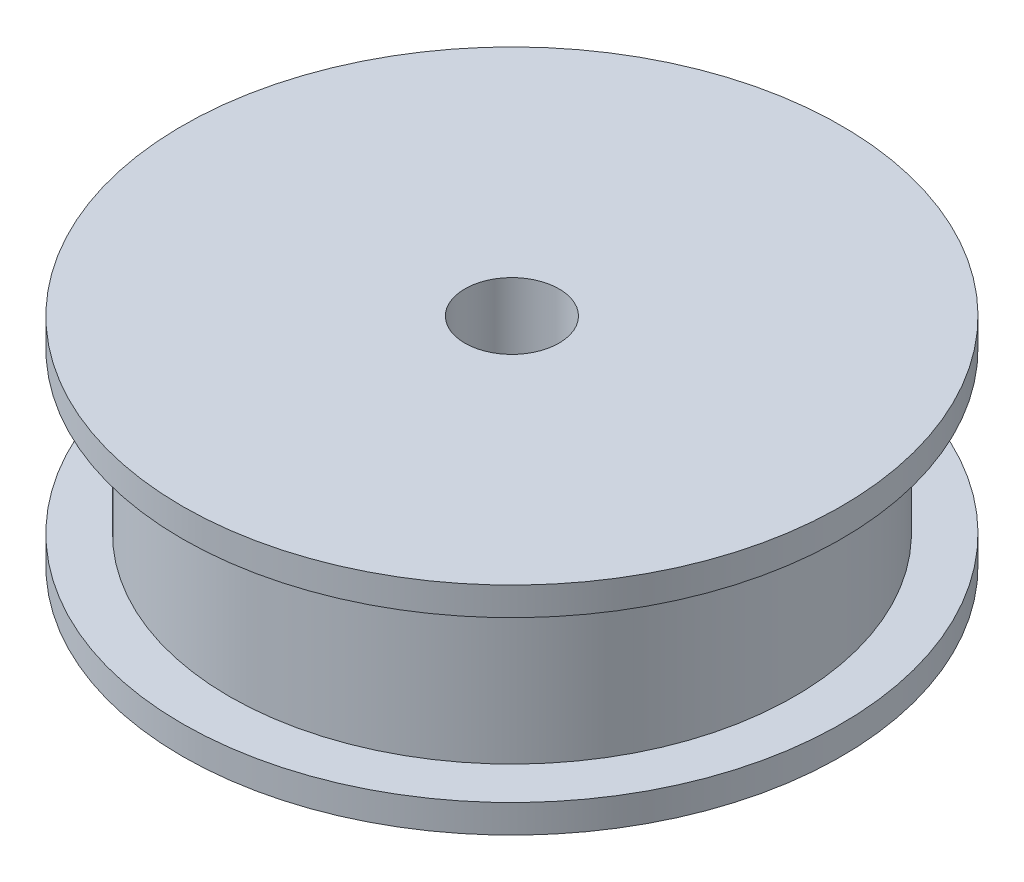
SolidWorks part; units mm, degrees
ref_plane "前视基准面" through (0, 0, 0) normal (0, 0, 1) x (1, 0, 0)
ref_plane "上视基准面" through (0, 0, 0) normal (0, 1, 0) x (1, 0, 0)
ref_plane "右视基准面" through (0, 0, 0) normal (1, 0, 0) x (0, 0, -1)
sketch "内环" plane through (0, 0, 0) normal (0, 1, 0) x (1, 0, 0)
  circle A0 centre (0, 0) radius 15
extrude "凸台-拉伸1" add sketch "内环" along normal mid plane 10
sketch "边缘" plane through (0, 0, 0) normal (0, 1, 0) x (1, 0, 0)
  circle A0 centre (0, 0) radius 17.5
extrude "边缘1" add sketch "边缘" along normal blind 1.5 from surface starting at face at (0, 5, 15)
extrude "边缘2" add sketch "草图2<2>" along normal blind 1.5 from surface starting at face at (0, -5, 15)
sketch "草图2<2>" plane through (0, 0, 0) normal (0, 1, 0) x (1, 0, 0) same geometry as "边缘"
sketch "孔" plane through (0, 0, 0) normal (0, 1, 0) x (1, 0, 0)
  circle A0 centre (0, 0) radius 2.5
extrude "切除-拉伸1" cut sketch "孔" against normal mid plane 13
